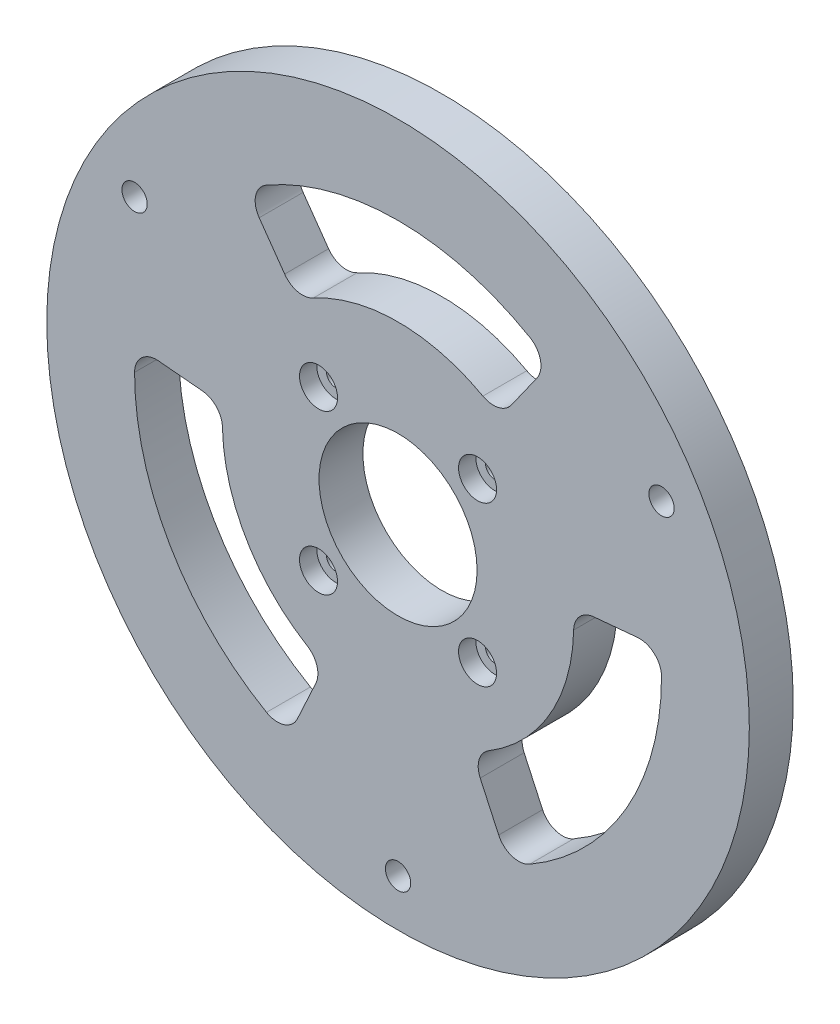
SolidWorks part; units mm, degrees
material "Acrylic (Medium-high impact)"
ref_plane "Front Plane" through (0, 0, 0) normal (0, 0, 1) x (1, 0, 0)
ref_plane "Top Plane" through (0, 0, 0) normal (0, 1, 0) x (1, 0, 0)
ref_plane "Right Plane" through (0, 0, 0) normal (1, 0, 0) x (0, 0, -1)
sketch "Sketch1" plane through (0, 0, 0) normal (0, 0, 1) x (1, 0, 0)
  circle A0 centre (0, 0) radius 50.8
  dimension "D1" = 101.6
extrude "Boss-Extrude1" add sketch "Sketch1" along normal blind 6.35
sketch "Sketch2" plane through (0, 0, 6.35) normal (0, 0, 1) x (1, 0, 0)
  circle A0 centre (0, 0) radius 11.43
  dimension "D1" = 22.86
extrude "Cut-Extrude1" cut sketch "Sketch2" against normal through all
hole_wizard "CBORE for M2.5 SHCS1" positions "Sketch3" profile "Sketch5" counterbore size "M2.5" standard "ANSI Metric"
sketch "Sketch3" plane through (0, 0, 6.35) normal (0, 0, 1) x (1, 0, 0)
  line L1 (-11.5, -11.5) -> (11.5, -11.5)
  line L2 (-11.5, -11.5) -> (-11.5, 11.5)
  line L3 (-11.5, 11.5) -> (11.5, 11.5)
  line L4 (11.5, -11.5) -> (11.5, 11.5)
  line L5 (-11.5, -11.5) -> (11.5, 11.5) construction
  line L6 (-11.5, 11.5) -> (11.5, -11.5) construction
  point P1 (0, 0)
  point P2 (11.5, 11.5)
  point P59 (-11.5, -11.5)
  point P60 (-11.5, 11.5)
  point P61 (11.5, -11.5)
  dimension "D1" = 23
sketch "Sketch5" plane through (0, 0, 6.35) normal (1, 0, 0) x (0, -1, 0)
  line L0 (0, 0) -> (0, 10.9712)
  line L1 (0, 10.9712) -> (1.35, 10.16)
  line L2 (1.35, 10.16) -> (1.35, 2.5)
  line L3 (1.35, 2.5) -> (2.75, 2.5)
  line L4 (2.75, 2.5) -> (2.75, 0)
  line L5 (2.75, 0) -> (0, 0)
  line L10 (0, 10.9712) -> (-1.35, 10.16) construction
  line L11 (0, -6.35) -> (0, 107.95) construction
  dimension "Hole Dia." = 2.7
  dimension "Hole Depth" = 10.16
  dimension "C'Bore Dia." = 5.5
  dimension "C'Bore Depth" = 2.5
  dimension "Drill Angle" = 118
hole_wizard "#6 Clearance Hole1" positions "Sketch7" profile "Sketch9" hole size "#6" standard "ANSI Inch"
sketch "Sketch7" plane through (0, 0, 6.35) normal (0, 0, 1) x (1, 0, 0)
  line L1 (0, -43.9941) -> (38.1, 21.997)
  line L2 (38.1, 21.997) -> (-38.1, 21.997)
  line L3 (-38.1, 21.997) -> (0, -43.9941)
  line L8 (-11.5, 11.5) -> (11.5, 11.5) construction
  circle A0 centre (0, 0) radius 21.997 construction
  point P3 (0, -43.9941)
  point P4 (38.1, 21.997)
  point P5 (-38.1, 21.997)
  dimension "D1" = 76.2
sketch "Sketch9" plane through (-38.1, 21.997, 6.35) normal (1, 0, 0) x (0, -1, 0)
  line L0 (0, 0) -> (0, 11.2589)
  line L1 (0, 11.2589) -> (1.8288, 10.16)
  line L2 (1.8288, 10.16) -> (1.8288, 0)
  line L5 (1.8288, 0) -> (0, 0)
  line L10 (0, 11.2589) -> (-1.8288, 10.16) construction
  line L11 (0, -6.35) -> (0, 107.95) construction
  dimension "Hole Dia." = 3.6576
  dimension "Hole Depth" = 10.16
  dimension "Drill Angle" = 118
fillet "Fillet1" [suppressed] radius 0.508
sketch "Sketch10" plane through (0, 0, 6.35) normal (0, 0, 1) x (1, 0, 0)
  line L0 (0, 0) -> (-21.9974, 31.1083) construction
  line L1 (0, 0) -> (21.9974, 31.1083) construction
  line L2 (14.6649, 20.7388) -> (21.9974, 31.1083)
  line L3 (-14.6649, 20.7388) -> (-21.9974, 31.1083)
  circle A0 centre (0, 0) radius 25.4 construction
  circle A1 centre (0, 0) radius 38.1 construction
  arc A4 (-21.9974, 31.1083) -> (21.9974, 31.1083) centre (0, 0) cw
  arc A5 (-14.6649, 20.7388) -> (14.6649, 20.7388) centre (0, 0) cw
  circle A6 centre (11.5, 11.5) radius 2.75 construction
  circle A7 centre (-11.5, 11.5) radius 2.75 construction
  point P5 (27.3788, 34.4366)
  point P14 (0, 0)
  dimension "D1" = 50.8
  dimension "D2" = 12.7
extrude "Cut-Extrude2" cut sketch "Sketch10" against normal through all
fillet "Fillet2" radius 3.175 4 edges at (-14.6649, 20.7388, 3.175) (14.6649, 20.7388, 3.175) (21.9974, 31.1083, 3.175) (-21.9974, 31.1083, 3.175)
pattern_circular "CirPattern1" count 3 over 360 about axis through (0, 0, 6.35) along (0, 0, 1) of "Cut-Extrude2", "Fillet2"
